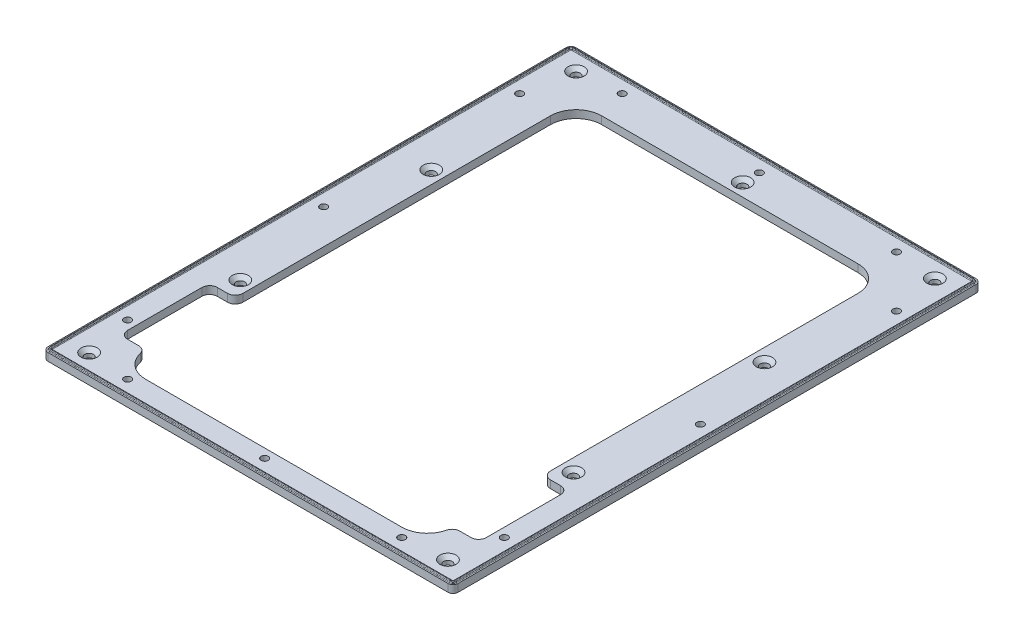
SolidWorks part; units mm, degrees
ref_plane "Front Plane" through (0, 0, 0) normal (0, 0, 1) x (1, 0, 0)
ref_plane "Top Plane" through (0, 0, 0) normal (0, 1, 0) x (1, 0, 0)
ref_plane "Right Plane" through (0, 0, 0) normal (1, 0, 0) x (0, 0, -1)
sketch "Sketch1" plane through (0, 0, 0) normal (0, 1, 0) x (1, 0, 0)
  line L0 (160, -203) -> (160, -3) construction
  line L1 (2, 0) -> (158, 0)
  line L2 (0, -2) -> (0, -204)
  line L3 (2, -206) -> (158, -206)
  line L4 (160, -2) -> (160, -204)
  line L5 (2, -206) -> (158, -206) construction
  arc A0 (0, -204) -> (2, -206) centre (2, -204) ccw
  arc A1 (158, -206) -> (160, -204) centre (158, -204) ccw
  arc A2 (158, 0) -> (160, -2) centre (158, -2) cw
  arc A3 (2, 0) -> (0, -2) centre (2, -2) ccw
  point P13 (160, -206)
  point P16 (160, 0)
  point P19 (0, 0)
  dimension "D3" = 2
  dimension "D1" = 160
  dimension "D2" = 206
extrude "Boss-Extrude1" add sketch "Sketch1" along normal blind 3
sketch "Sketch12" plane through (0, 3, 0) normal (0, 1, 0) x (1, 0, 0)
  circle A0 centre (80, -13) radius 3 construction
  circle A1 centre (10, -8) radius 1.6 construction
  circle A2 centre (15, -69.5) radius 3 construction
  circle A3 centre (15, -144) radius 3 construction
  circle A4 centre (10, -198) radius 1.6 construction
  circle A5 centre (150, -198) radius 2.1 construction
  circle A6 centre (145, -144) radius 3 construction
  circle A7 centre (145, -69.5) radius 3 construction
  circle A8 centre (150, -8) radius 1.6 construction
  circle A9 centre (80, -13) radius 3
  circle A10 centre (10, -8) radius 1.6
  circle A11 centre (15, -69.5) radius 3
  circle A12 centre (15, -144) radius 3
  circle A13 centre (10, -198) radius 1.6
  circle A14 centre (150, -198) radius 2.1
  circle A15 centre (145, -144) radius 3
  circle A16 centre (145, -69.5) radius 3
  circle A17 centre (150, -8) radius 1.6
hole_wizard "CSK for M3 Flat Head Machine Screw1" positions "3DSketch1" profile "Sketch13" countersink size "M3" standard "ANSI Metric" end condition through all
sketch3d "3DSketch1"
  point P0 (10, 3, 8)
  point P3 (80, 3, 13)
  point P6 (150, 3, 8)
  point P9 (145, 3, 69.5)
  point P12 (15, 3, 69.5)
  point P15 (15, 3, 144)
  point P18 (10, 3, 198)
  point P21 (150, 3, 198)
  point P24 (145, 3, 144)
sketch "Sketch13" plane through (10, 3, 8) normal (1, 0, 0) x (0, 0, 1)
  line L0 (0, 0) -> (0, 3)
  line L1 (0, 3) -> (1.7, 3)
  line L2 (1.7, 3) -> (1.7, 1.45)
  line L3 (1.7, 1.45) -> (3.15, 0)
  line L5 (3.15, 0) -> (0, 0)
  line L6 (-1.7, 1.45) -> (-3.15, 0) construction
  line L11 (0, -6.35) -> (0, 107.95) construction
  dimension "Thru Hole Dia." = 3.4
  dimension "Thru Hole Depth" = 3
  dimension "Near C'Sink Dia." = 6.3
  dimension "Near C'Sink Angle" = 90
sketch "Sketch14" plane through (0, 3, 0) normal (0, 1, 0) x (1, 0, 0)
  line L0 (2, -206) -> (158, -206) construction
  line L1 (30, -18) -> (130, -18)
  line L2 (20, -28) -> (20, -186)
  line L3 (30, -196) -> (130, -196)
  line L4 (140, -28) -> (140, -186)
  circle A0 centre (80, -13) radius 3.15 construction
  circle A1 centre (145, -69.5) radius 3.15 construction
  circle A2 centre (15, -69.5) radius 3.15 construction
  arc A3 (20, -186) -> (30, -196) centre (30, -186) ccw
  arc A4 (130, -196) -> (140, -186) centre (130, -186) ccw
  arc A5 (130, -18) -> (140, -28) centre (130, -28) cw
  arc A6 (30, -18) -> (20, -28) centre (30, -28) ccw
  dimension "D1" = 5
  dimension "D2" = 5
  dimension "D3" = 5
  dimension "D5" = 10
  dimension "D4" = 10
extrude "Cut-Extrude8" cut sketch "Sketch14" against normal through all
sketch "Sketch15" plane through (0, 3, 0) normal (0, 1, 0) x (1, 0, 0)
  line L0 (20, -28) -> (20, -186) construction
  line L1 (20, -151) -> (10, -151)
  line L2 (20, -151) -> (20, -186)
  line L3 (20, -186) -> (10, -186)
  line L4 (10, -151) -> (10, -186)
  line L5 (140, -186) -> (140, -28) construction
  line L6 (140, -151) -> (150, -151)
  line L7 (140, -151) -> (140, -186)
  line L8 (140, -186) -> (150, -186)
  line L9 (150, -151) -> (150, -186)
  point P12 (20, -188.8925)
  point P13 (20, -186)
  point P15 (150, -190.5848)
  dimension "D1" = 35
  dimension "D2" = 10
extrude "Cut-Extrude9" cut sketch "Sketch15" against normal through all
fillet "Fillet5" radius 3 8 edges at (150, 1.5, 186) (140, 1.5, 151) (150, 1.5, 151) (10, 1.5, 186) (20, 1.5, 186) (10, 1.5, 151) (20, 1.5, 151) (140, 1.5, 186)
ref_plane "Plane3" through (0, 0, 103) normal (0, 0, -1) x (-1, 0, 0)
ref_plane "Plane4" through (80, 0, 0) normal (-1, 0, 0) x (0, 0, 1)
ref_axis "Axis1" through (80, -0.15, 103) along (0, 1, 0)
sketch "Sketch18" plane through (0, 3, 0) normal (0, 1, 0) x (1, 0, 0)
  line L8 (2, -205.25) -> (158, -205.25)
  line L9 (159.25, -204) -> (159.25, -2)
  line L10 (158, -0.75) -> (2, -0.75)
  line L11 (0.75, -2) -> (0.75, -204)
  line L12 (2, -205.25) -> (158, -205.25)
  line L13 (159.25, -204) -> (159.25, -2)
  line L14 (158, -0.75) -> (2, -0.75)
  line L15 (0.75, -2) -> (0.75, -204)
  line L20 (2, -204.5) -> (158, -204.5)
  line L21 (158.5, -204) -> (158.5, -2)
  line L22 (158, -1.5) -> (2, -1.5)
  line L23 (1.5, -2) -> (1.5, -204)
  line L24 (2, -204.5) -> (158, -204.5)
  line L25 (158.5, -204) -> (158.5, -2)
  line L26 (158, -1.5) -> (2, -1.5)
  line L27 (1.5, -2) -> (1.5, -204)
  arc A8 (0.75, -204) -> (2, -205.25) centre (2, -204) ccw
  arc A9 (158, -205.25) -> (159.25, -204) centre (158, -204) ccw
  arc A10 (159.25, -2) -> (158, -0.75) centre (158, -2) ccw
  arc A11 (2, -0.75) -> (0.75, -2) centre (2, -2) ccw
  arc A12 (0.75, -204) -> (2, -205.25) centre (2, -204) ccw
  arc A13 (158, -205.25) -> (159.25, -204) centre (158, -204) ccw
  arc A14 (159.25, -2) -> (158, -0.75) centre (158, -2) ccw
  arc A15 (2, -0.75) -> (0.75, -2) centre (2, -2) ccw
  arc A20 (1.5, -204) -> (2, -204.5) centre (2, -204) ccw
  arc A21 (158, -204.5) -> (158.5, -204) centre (158, -204) ccw
  arc A22 (158.5, -2) -> (158, -1.5) centre (158, -2) ccw
  arc A23 (2, -1.5) -> (1.5, -2) centre (2, -2) ccw
  arc A24 (1.5, -204) -> (2, -204.5) centre (2, -204) ccw
  arc A25 (158, -204.5) -> (158.5, -204) centre (158, -204) ccw
  arc A26 (158.5, -2) -> (158, -1.5) centre (158, -2) ccw
  arc A27 (2, -1.5) -> (1.5, -2) centre (2, -2) ccw
  dimension "D1" = 0.75
  dimension "D2" = 1.5
extrude "Boss-Extrude2" add sketch "Sketch18" along normal blind 0.5
fillet "Fillet6" radius 0.25 32 edges at (1.1161, 3, 1.1161) (80, 3, 0.75) (158.8839, 3, 1.1161) (159.25, 3, 103) (158.8839, 3, 204.8839) (80, 3, 205.25) (1.1161, 3, 204.8839) (158.3536, 3, 1.6464) (158.5, 3, 103) (158.3536, 3, 204.3536) (80, 3, 204.5) (1.6464, 3, 204.3536) (1.5, 3, 103) (1.6464, 3, 1.6464) (80, 3.5, 1.5) (158.3536, 3.5, 1.6464) (158.5, 3.5, 103) (158.3536, 3.5, 204.3536) (80, 3.5, 204.5) (1.6464, 3.5, 204.3536) (1.5, 3.5, 103) (80, 3.5, 0.75) (158.8839, 3.5, 1.1161) (159.25, 3.5, 103) (158.8839, 3.5, 204.8839) (80, 3.5, 205.25) (1.1161, 3.5, 204.8839) (0.75, 3.5, 103) (0.75, 3, 103) (80, 3, 1.5) (1.6464, 3.5, 1.6464) (1.1161, 3.5, 1.1161)
hole_wizard "Ø3.0mm Dowel Hole1" positions "3DSketch3" profile "Sketch21" hole size "Ø3.0" standard "ANSI Metric" end condition through all
sketch3d "3DSketch3"
  line L0 (133.5, 8.5, 6.5) -> (133.5, 3, 6.5) construction
  line L1 (80, 8.5, 6.5) -> (80, 3, 6.5) construction
  line L2 (26.5, 8.5, 6.5) -> (26.5, 3, 6.5) construction
  line L3 (6.5, 8.5, 26.5) -> (6.5, 3, 26.5) construction
  line L4 (6.5, 8.5, 103) -> (6.5, 3, 103) construction
  line L5 (6.5, 8.5, 179.5) -> (6.5, 3, 179.5) construction
  line L6 (26.5, 8.5, 199.5) -> (26.5, 3, 199.5) construction
  line L7 (80, 8.5, 199.5) -> (80, 3, 199.5) construction
  line L8 (133.5, 8.5, 199.5) -> (133.5, 3, 199.5) construction
  line L9 (153.5, 8.5, 179.5) -> (153.5, 3, 179.5) construction
  line L10 (153.5, 8.5, 103) -> (153.5, 3, 103) construction
  line L11 (153.5, 8.5, 26.5) -> (153.5, 3, 26.5) construction
  point P0 (133.5, 3, 6.5)
  point P4 (80, 8.5, 6.5)
  point P8 (26.5, 3, 6.5)
  point P12 (6.5, 8.5, 26.5)
  point P16 (6.5, 8.5, 103)
  point P20 (6.5, 8.5, 179.5)
  point P24 (26.5, 3, 199.5)
  point P28 (80, 8.5, 199.5)
  point P32 (133.5, 3, 199.5)
  point P36 (153.5, 8.5, 179.5)
  point P40 (153.5, 8.5, 103)
  point P44 (153.5, 3, 26.5)
  point P50 (133.5, 8.5, 6.5)
  point P52 (153.5, 8.5, 26.5)
  point P54 (26.5, 8.5, 6.5)
  point P56 (26.5, 8.5, 199.5)
  point P58 (133.5, 8.5, 199.5)
sketch "Sketch21" plane through (133.5, 3, 6.5) normal (1, 0, 0) x (0, 0, -1)
  line L0 (0, 0) -> (0, 0.5)
  line L1 (0, 0.5) -> (1.4, 0.5)
  line L2 (1.4, 0.5) -> (1.4, 0)
  line L5 (1.4, 0) -> (0, 0)
  line L11 (0, -6.35) -> (0, 107.95) construction
  dimension "Thru Hole Dia." = 2.8
  dimension "Thru Hole Depth" = 0.5
